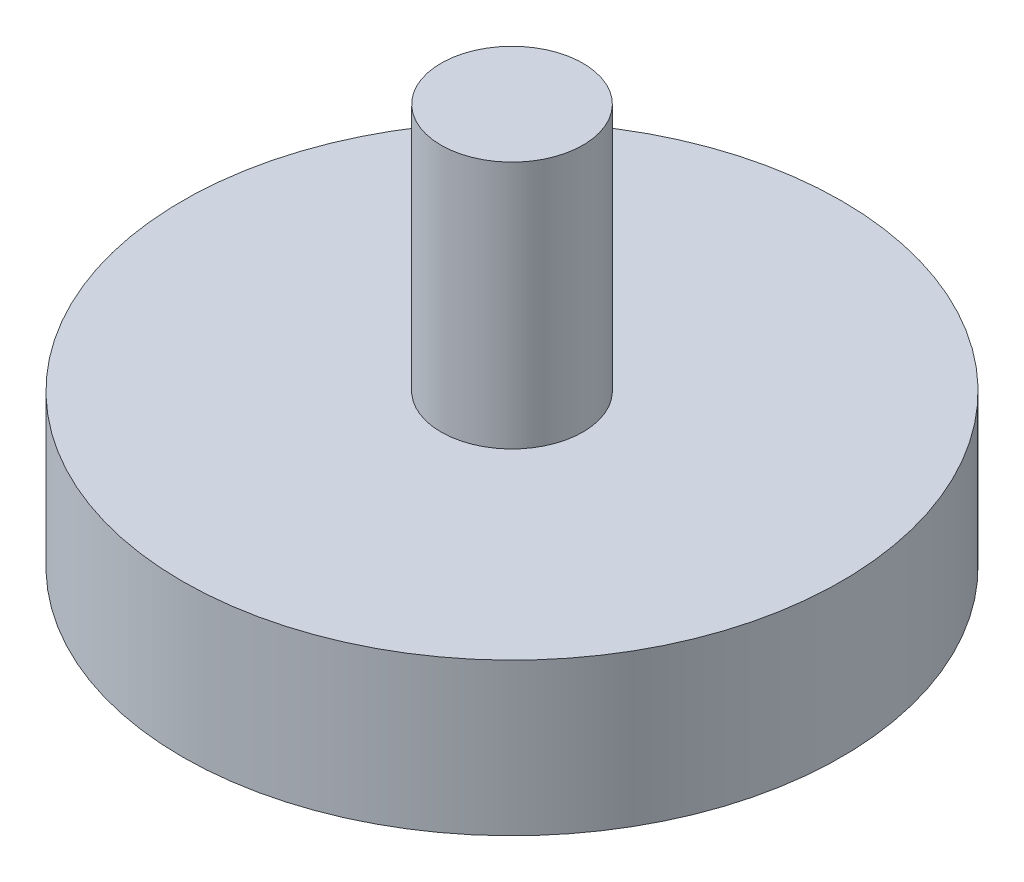
SolidWorks part; units mm, degrees
ref_plane "Front Plane" through (0, 0, 0) normal (0, 0, 1) x (1, 0, 0)
ref_plane "Top Plane" through (0, 0, 0) normal (0, 1, 0) x (1, 0, 0)
ref_plane "Right Plane" through (0, 0, 0) normal (1, 0, 0) x (0, 0, -1)
sketch "Sketch1" plane through (0, 0, 0) normal (0, 1, 0) x (1, 0, 0)
  circle A0 centre (0, 0) radius 16.51
  circle A1 centre (0, 0) radius 3.556
  dimension "D1" = 33.02
  dimension "D2" = 7.112
extrude "Boss-Extrude1" add sketch "Sketch1" along normal blind 12.446 contours A1 region at (0, 0, 0)
extrude "Boss-Extrude2" add sketch "Sketch1<3>" against normal blind 7.62 separate body contours A1 | A0 A1 region at (-16.043, 0, 0) region at (0, 0, 0)
sketch "Sketch1<3>" plane through (0, 0, 0) normal (0, 1, 0) x (1, 0, 0) same geometry as "Sketch1"
